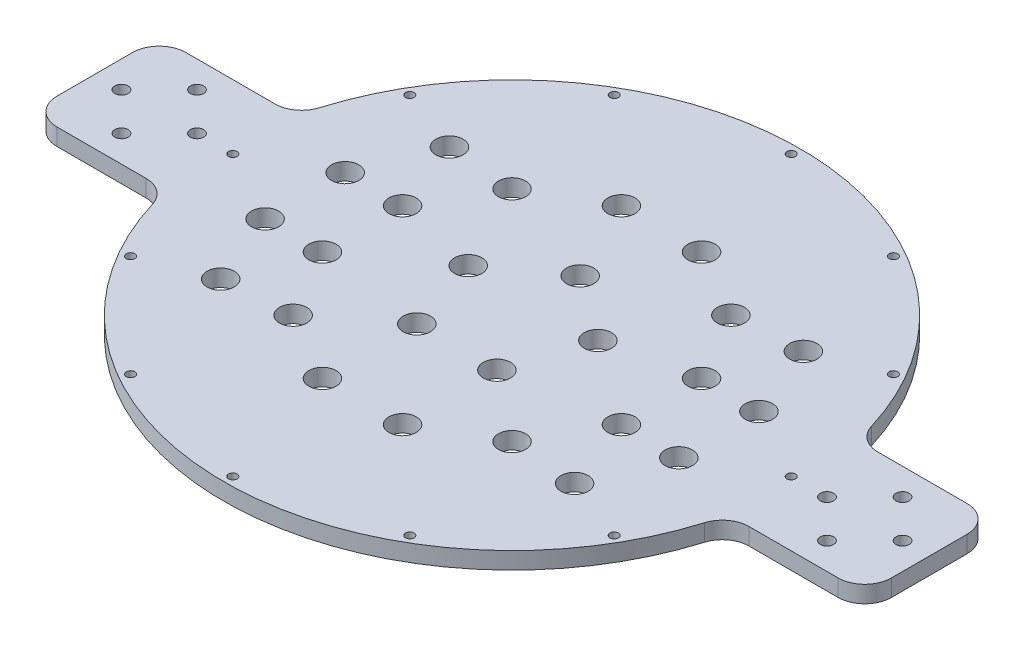
SolidWorks part; units mm, degrees
material "AISI 304"
ref_plane "Front Plane" through (0, 0, 0) normal (0, 0, 1) x (1, 0, 0)
ref_plane "Top Plane" through (0, 0, 0) normal (0, 1, 0) x (1, 0, 0)
ref_plane "Right Plane" through (0, 0, 0) normal (1, 0, 0) x (0, 0, -1)
sketch "Sketch1" plane through (0, 0, 0) normal (0, 1, 0) x (1, 0, 0)
  circle A1 centre (0, 0) radius 107.95
  dimension "D2" = 215.9
extrude "Boss-Extrude1" add sketch "Sketch1" along normal blind 6.35
hole_wizard "M3 Clearance Hole1" positions "Sketch9" profile "Sketch10" hole size "M3" standard "ANSI Metric" end condition through all
sketch "Sketch9" plane through (0, 6.35, 0) normal (0, 1, 0) x (1, 0, 0)
  line L0 (0, 0) -> (0, 104.55) construction
  point P2 (0, 104.55)
  point P4 (0, 0)
  dimension "D1" = 104.55
sketch "Sketch10" plane through (0, 6.35, -104.55) normal (1, 0, 0) x (0, 0, 1)
  line L0 (0, 0) -> (0, 6.35)
  line L1 (0, 6.35) -> (1.6, 6.35)
  line L2 (1.6, 6.35) -> (1.6, 0)
  line L5 (1.6, 0) -> (0, 0)
  line L11 (0, -6.35) -> (0, 107.95) construction
  dimension "Thru Hole Dia." = 3.2
  dimension "Thru Hole Depth" = 6.35
pattern_circular "CirPattern1" count 12 over 360 about axis through (0, 6.35, 0) along (0, -1, 0) of "M3 Clearance Hole1" reverse direction yes
sketch "Sketch2" plane through (0, 0, 0) normal (0, 1, 0) x (1, 0, 0)
  line L0 (-156.2343, 24.1421) -> (-105.2158, 24.1421)
  line L1 (-105.2158, -24.1421) -> (-156.2343, -24.1421)
  line L2 (-156.2343, -24.1421) -> (-156.2343, 24.1421)
  line L3 (-156.2343, 0) -> (0, 0) construction
  line L4 (-146.2343, 0) -> (-132.0921, 14.1421) construction
  line L5 (-132.0921, 14.1421) -> (-117.95, 0) construction
  line L6 (-117.95, 0) -> (-132.0921, -14.1421) construction
  line L7 (-132.0921, -14.1421) -> (-146.2343, 0) construction
  circle A0 centre (0, 0) radius 107.95 construction
  circle A1 centre (0, 0) radius 107.95 construction
  arc A2 (-105.2158, 24.1421) -> (-105.2158, -24.1421) centre (0, 0) ccw
  point P11 (-107.95, 0)
  dimension "D1" = 20
  dimension "D2" = 10
  dimension "D3" = 10
  dimension "D4" = 10
extrude "Boss-Extrude2" add sketch "Sketch2" along normal up to surface (6.35 mm away) up to face at (52.275, 6.35, -88.943)
hole_wizard "#10 Clearance Hole3" positions "Sketch7" profile "Sketch8" hole size "#10" standard "ANSI Inch" end condition through all
sketch "Sketch7" plane through (0, 6.35, 0) normal (0, 1, 0) x (1, 0, 0)
  line L0 (-117.95, 0) -> (-132.0921, -14.1421) construction
  line L1 (-132.0921, -14.1421) -> (-146.2343, 0) construction
  line L2 (-146.2343, 0) -> (-132.0921, 14.1421) construction
  line L3 (-132.0921, 14.1421) -> (-117.95, 0) construction
  line L4 (-117.95, 0) -> (-132.0921, -14.1421) construction
  line L5 (-132.0921, -14.1421) -> (-146.2343, 0) construction
  line L6 (-146.2343, 0) -> (-132.0921, 14.1421) construction
  line L7 (-132.0921, 14.1421) -> (-117.95, 0) construction
  point P0 (-132.0921, -14.1421)
  point P2 (-117.95, 0)
  point P4 (-132.0921, 14.1421)
  point P6 (-146.2343, 0)
sketch "Sketch8" plane through (-132.0921, 6.35, 14.1421) normal (1, 0, 0) x (0, 0, 1)
  line L0 (0, 0) -> (0, 6.35)
  line L1 (0, 6.35) -> (2.4892, 6.35)
  line L2 (2.4892, 6.35) -> (2.4892, 0)
  line L5 (2.4892, 0) -> (0, 0)
  line L11 (0, -6.35) -> (0, 107.95) construction
  dimension "Thru Hole Dia." = 4.9784
  dimension "Thru Hole Depth" = 6.35
fillet "Fillet1" radius 10 4 edges at (-105.2158, 3.175, -24.1421) (-156.2343, 3.175, -24.1421) (-156.2343, 3.175, 24.1421) (-105.2158, 3.175, 24.1421)
mirror "Mirror1" about plane through (0, 0, 0) normal (1, 0, 0) of "#10 Clearance Hole3", "Fillet1", "Boss-Extrude2"
sketch "Sketch11" plane through (0, 6.35, 0) normal (0, 1, 0) x (1, 0, 0)
  line L0 (-88.9, 0) -> (0, 0) construction
  line L1 (0, 0) -> (0, 88.9) construction
  circle A0 centre (0, 0) radius 88.9 construction
  circle A1 centre (-66.2622, 42.8314) radius 5.1
  circle A2 centre (-77.461, 15) radius 5.1
  circle A3 centre (-77.461, -15) radius 5.1
  circle A4 centre (-66.2622, -42.8314) radius 5.1
  circle A9 centre (0, 25.5195) radius 5.1
  circle A10 centre (-24.2705, 7.886) radius 5.1
  circle A11 centre (24.2705, 7.886) radius 5.1
  circle A12 centre (-15, -20.6457) radius 5.1
  circle A13 centre (15, -20.6457) radius 5.1
  circle A14 centre (-55.9808, -15) radius 5.1
  circle A15 centre (-40.9808, -40.9808) radius 5.1
  circle A16 centre (-15, -55.9808) radius 5.1
  circle A17 centre (15, -55.9808) radius 5.1
  circle A18 centre (-55.9808, 15) radius 5.1
  circle A20 centre (55.9808, -15) radius 5.1
  circle A21 centre (40.9808, -40.9808) radius 5.1
  circle A26 centre (0, 0) radius 25.5195 construction
  arc A27 (-64.809, 45) -> (-64.809, -45) centre (0, 0) ccw construction
  circle A28 centre (66.2622, -42.8314) radius 5.1
  circle A29 centre (77.461, -15) radius 5.1
  circle A30 centre (77.461, 15) radius 5.1
  circle A31 centre (66.2622, 42.8314) radius 5.1
  circle A32 centre (0, 0) radius 57.9555 construction
  circle A33 centre (55.9808, 15) radius 5.1
  circle A34 centre (40.9808, 40.9808) radius 5.1
  circle A35 centre (15, 55.9808) radius 5.1
  circle A36 centre (-15, 55.9808) radius 5.1
  circle A37 centre (-40.9808, 40.9808) radius 5.1
  point P55 (0, 0)
  point P57 (-29.0983, -70.4231)
  point P58 (33.5089, -46.3693)
  point P59 (49.6603, -28.4044)
  point P60 (49.6603, 28.4044)
  point P63 (0, 0)
  point P65 (0, 0)
  point P66 (0, 0)
  point P67 (49.6035, 24.0364)
  point P68 (0, 0)
  point P69 (0, 0)
  point P70 (0, 0)
  point P71 (-29.4765, -49.8997)
  point P72 (-44.9124, -36.6295)
  point P73 (-53.0067, -23.4336)
  point P74 (-57.6446, 5.9951)
  dimension "D1" = 177.8
  dimension "D2" = 10.2
  dimension "D3" = 30
  dimension "D8" = 10
  dimension "D9" = 90
  dimension "D11" = 30
  dimension "D4" = 30
  dimension "D5" = 30
  dimension "D6" = 30
  dimension "D7" = 30
  dimension "D10" = 30
  dimension "D12" = 30
  dimension "D13" = 30
  dimension "D14" = 30
  dimension "D15" = 30
  dimension "D16" = 30
  dimension "D17" = 30
  dimension "D18" = 30
  dimension "D19" = 30
extrude "Cut-Extrude1" cut sketch "Sketch11" against normal up to next (6.35 mm away)
